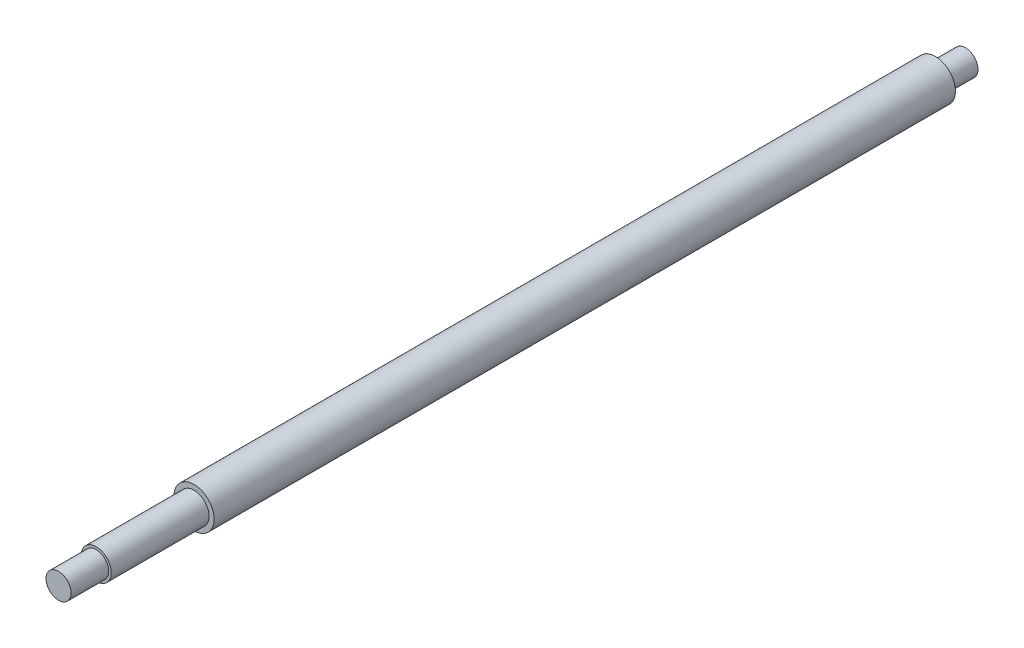
SolidWorks part; units mm, degrees
material "1060 Alloy"
ref_plane "Front Plane" through (0, 0, 0) normal (0, 0, 1) x (1, 0, 0)
ref_plane "Top Plane" through (0, 0, 0) normal (0, 1, 0) x (1, 0, 0)
ref_plane "Right Plane" through (0, 0, 0) normal (1, 0, 0) x (0, 0, -1)
sketch "Sketch1" plane through (0, 0, 0) normal (1, 0, 0) x (0, 0, -1)
  line L0 (0, 0) -> (-42.623, 0) construction
  line L1 (-350.13, 0) -> (-350.13, 5)
  line L2 (-350.13, 5) -> (-335.13, 5)
  line L3 (-335.13, 5) -> (-335.13, 6)
  line L4 (-335.13, 6) -> (-296.13, 6)
  line L5 (-296.13, 6) -> (-296.13, 8)
  line L6 (-296.13, 8) -> (-0.68, 8)
  line L7 (-0.68, 8) -> (-0.68, 5)
  line L8 (-0.68, 5) -> (11.32, 5)
  line L9 (11.32, 5) -> (11.32, 0)
  line L10 (-350.13, 0) -> (11.32, 0)
  line L12 (-6.68, 0) -> (-6.68, -14) construction
  point P2 (-139.727, -14)
  point P4 (0, 0)
  point P6 (0, 0)
  point P15 (0, 0)
  point P16 (-6.68, 0)
  point P19 (0, 0)
  point P20 (11.32, 0)
  point P22 (0, 0)
  point P23 (0, 0)
  point P24 (0, 0)
  point P25 (0, 0)
  point P26 (0, 0)
  point P27 (0, 0)
  point P28 (0, 0)
  point P29 (0, 0)
  point P30 (0, 0)
  point P31 (0, 0)
  point P33 (11.32, 0)
  point P34 (-284.5518, 8)
  point P35 (-297.7361, 6)
  point P36 (0, 0)
  point P37 (-295.3502, 8)
  point P38 (0, 0)
  dimension "D1" = 5
  dimension "D2" = 6
  dimension "D3" = 8
  dimension "D4" = 5
  dimension "D5" = 12
  dimension "D6" = 39
  dimension "D7" = 15
  dimension "D8" = 18
  dimension "D9" = 133.7816
  dimension "D10" = 295.45
revolve "Revolve1" add sketch "Sketch1" angle 360 about L0
sketch "Sketch3" [suppressed] plane through (0, 0, 0) normal (1, 0, 0) x (0, 0, -1)
  line L0 (-80.9254, 0) -> (-123.5483, 0) construction
  line L1 (-275.75, 0) -> (-275.75, 5)
  line L2 (-275.75, 5) -> (-260.75, 5)
  line L3 (-260.75, 5) -> (-260.75, 6)
  line L4 (-260.75, 6) -> (-221.75, 6)
  line L5 (-221.75, 6) -> (-221.75, 8)
  line L6 (-221.75, 8) -> (-12, 8)
  line L7 (-12, 8) -> (-12, 5)
  line L8 (-12, 5) -> (0, 5)
  line L9 (0, 5) -> (0, 0)
  line L10 (-275.75, 0) -> (0, 0)
  dimension "D1" = 10
  dimension "D2" = 6
  dimension "D3" = 8
  dimension "D4" = 10
  dimension "D5" = 15
  dimension "D6" = 39
  dimension "D7" = 209.75
  dimension "D8" = 12
revolve "Revolve2" [suppressed] add sketch "Sketch3" angle 360 about L0
